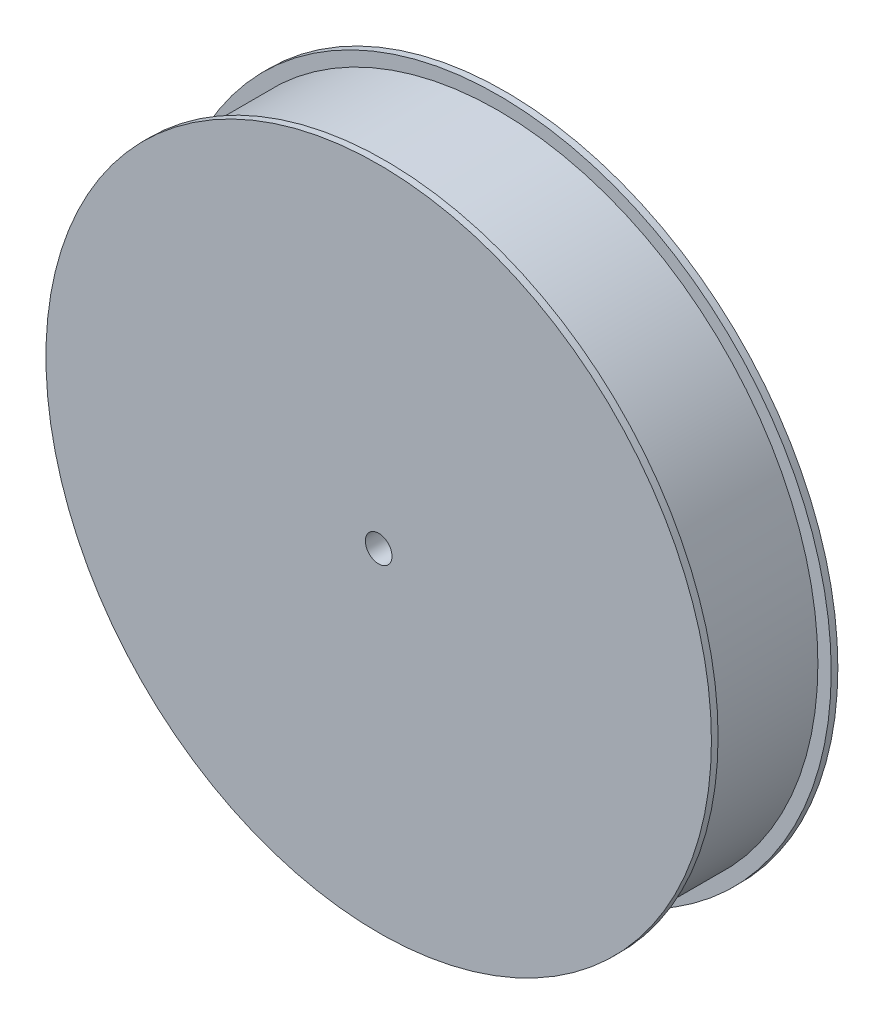
SolidWorks part; units mm, degrees
ref_plane "Front Plane" through (0, 0, 0) normal (0, 0, 1) x (1, 0, 0)
ref_plane "Top Plane" through (0, 0, 0) normal (0, 1, 0) x (1, 0, 0)
ref_plane "Right Plane" through (0, 0, 0) normal (1, 0, 0) x (0, 0, -1)
sketch "Inner" plane through (0, 0, 0) normal (0, 0, 1) x (1, 0, 0)
  circle A0 centre (0, 0) radius 76.2
  dimension "D1" = 152.4
extrude "Boss-Extrude1" add sketch "Inner" along normal blind 13.4937 contours A0
sketch "Rim" plane through (0, 0, 13.4937) normal (0, 0, 1) x (1, 0, 0)
  circle A0 centre (0, 0) radius 79.375
  circle A1 centre (0, 0) radius 76.2 construction
  dimension "D1" = 3.175
extrude "Boss-Extrude2" add sketch "Rim" along normal blind 1.5875
mirror "Mirror1" about plane through (0, 0, 0) normal (0, 0, 1) of bodies 102
sketch "Hole" plane through (0, 0, 15.0812) normal (0, 0, 1) x (1, 0, 0)
  circle A0 centre (0, 0) radius 3.175
  dimension "D1" = 6.35
extrude "Cut-Extrude1" cut sketch "Hole" against normal through all
